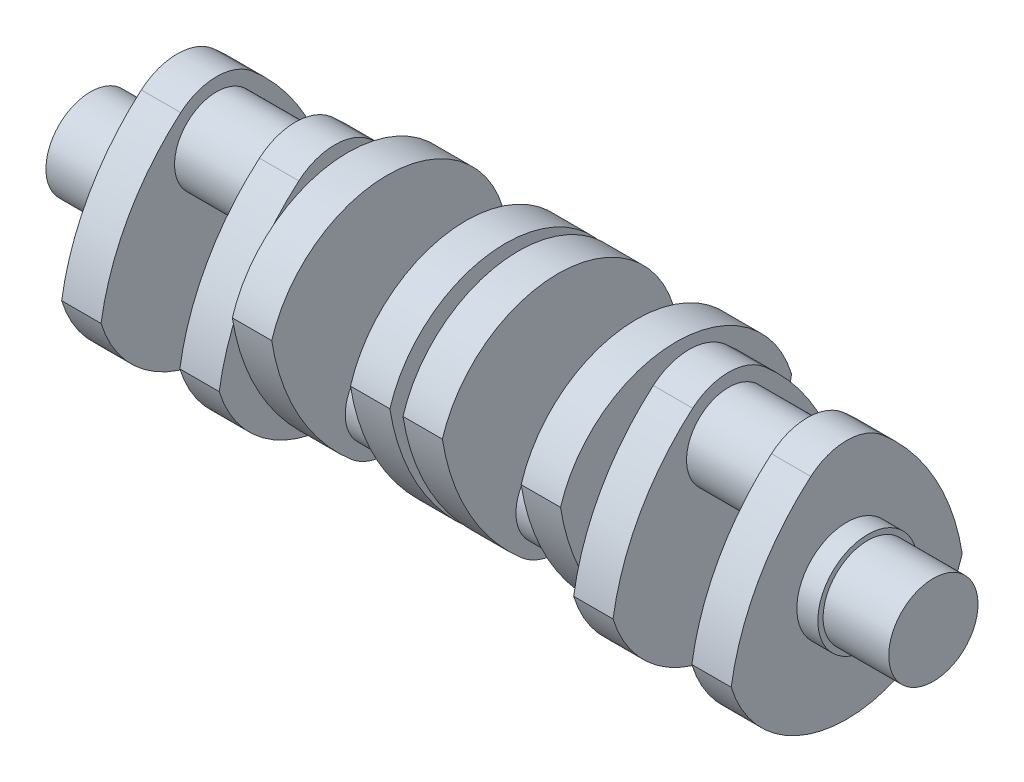
SolidWorks part; units mm, degrees
ref_plane "Front Plane" through (0, 0, 0) normal (0, 0, 1) x (1, 0, 0)
ref_plane "Top Plane" through (0, 0, 0) normal (0, 1, 0) x (1, 0, 0)
ref_plane "Right Plane" through (0, 0, 0) normal (1, 0, 0) x (0, 0, -1)
sketch "Sketch1" plane through (0, 0, 0) normal (1, 0, 0) x (0, 0, -1)
  circle A0 centre (0, 0) radius 19
  circle A1 centre (0, 0) radius 17
  dimension "D1" = 38
  dimension "D2" = 34
extrude "Boss-Extrude1" add sketch "Sketch1" against normal blind 25 contours A1 region at (0, 0, 0)
extrude "Boss-Extrude5" add sketch "Sketch1<6>" along normal blind 8 contours A1 | A0 A1 region at (0, 0, 18.4626) region at (0, 0, 0)
sketch "Sketch1<6>" plane through (0, 0, 0) normal (1, 0, 0) x (0, 0, -1) same geometry as "Sketch1"
sketch "Sketch2" plane through (8, 0, 0) normal (1, 0, 0) x (0, 0, -1)
  arc A0 (-13.6681, 40.9431) -> (13.6681, 40.9431) centre (0, 25) cw
  arc A4 (44, -13.4164) -> (-44, -13.4164) centre (0, 0) cw
  arc A5 (-13.6681, 40.9431) -> (-44, -13.4164) centre (44.9095, -27.3845) ccw
  arc A6 (13.6681, 40.9431) -> (44, -13.4164) centre (-44.9095, -27.3845) cw
  point P8 (0, 0)
  point P9 (0, 0)
  point P11 (0, 0)
  point P12 (0, 0)
  point P13 (0, 0)
  point P14 (0, 0)
  point P15 (0, 0)
  dimension "D2" = 21
  dimension "D3" = 90
  dimension "D4" = 90
  dimension "D6" = 46
  dimension "D1" = 88
  dimension "D5" = 25
extrude "Boss-Extrude6" add sketch "Sketch2" along normal blind 15
sketch "Sketch4" plane through (23, 0, 0) normal (1, 0, 0) x (0, 0, -1)
  circle A0 centre (0, 25) radius 16
  dimension "D1" = 32
extrude "Boss-Extrude7" add sketch "Sketch4" along normal blind 15
mirror "Mirror1" about plane through (38, 25, 0) normal (1, 0, 0) of "Boss-Extrude7", "Boss-Extrude6"
sketch "Sketch5" plane through (68, 0, 0) normal (1, 0, 0) x (0, 0, -1)
  circle A0 centre (0, 0) radius 17
  dimension "D1" = 34
extrude "Boss-Extrude8" add sketch "Sketch5" along normal blind 5
sketch "Sketch7" plane through (73, 0, 0) normal (1, 0, 0) x (0, 0, -1)
  circle A0 centre (0, 0) radius 17 construction
  arc A8 (-13.6681, -40.9431) -> (13.6681, -40.9431) centre (0, -25) ccw
  arc A9 (-44, 13.4164) -> (-13.6681, -40.9431) centre (44.9095, 27.3845) ccw
  arc A10 (44, 13.4164) -> (-44, 13.4164) centre (0, 0) ccw
  arc A11 (13.6681, -40.9431) -> (44, 13.4164) centre (-44.9095, 27.3845) ccw
  dimension "D1" = 21
  dimension "D2" = 90
  dimension "D3" = 46
  dimension "D4" = 13.6681
  dimension "D5" = 44
extrude "Boss-Extrude9" add sketch "Sketch7" along normal blind 15
sketch "Sketch8" plane through (88, 0, 0) normal (1, 0, 0) x (0, 0, -1)
  circle A0 centre (0, -25) radius 16
  dimension "D1" = 32
extrude "Boss-Extrude10" add sketch "Sketch8" along normal blind 30
sketch "Sketch9" plane through (118, 0, 0) normal (1, 0, 0) x (0, 0, -1)
  arc A4 (-13.6681, -40.9431) -> (13.6681, -40.9431) centre (0, -25) ccw
  arc A5 (13.6681, -40.9431) -> (44, 13.4164) centre (-44.9095, 27.3845) ccw
  arc A6 (44, 13.4164) -> (-44, 13.4164) centre (0, 0) ccw
  arc A7 (-44, 13.4164) -> (-13.6681, -40.9431) centre (44.9095, 27.3845) ccw
  arc A8 (-13.6681, -40.9431) -> (13.6681, -40.9431) centre (0, -25) ccw
  arc A9 (13.6681, -40.9431) -> (44, 13.4164) centre (-44.9095, 27.3845) ccw
  arc A10 (44, 13.4164) -> (-44, 13.4164) centre (0, 0) ccw
  arc A11 (-44, 13.4164) -> (-13.6681, -40.9431) centre (44.9095, 27.3845) ccw
  dimension "D1" = 0
extrude "Boss-Extrude11" add sketch "Sketch9" along normal blind 15
sketch "Sketch10" plane through (133, 0, 0) normal (1, 0, 0) x (0, 0, -1)
  circle A0 centre (0, 0) radius 17
  dimension "D1" = 34
extrude "Boss-Extrude12" add sketch "Sketch10" along normal blind 2.5
mirror "Mirror2" about plane through (135.5, 0, 0) normal (1, 0, 0) of bodies 113
